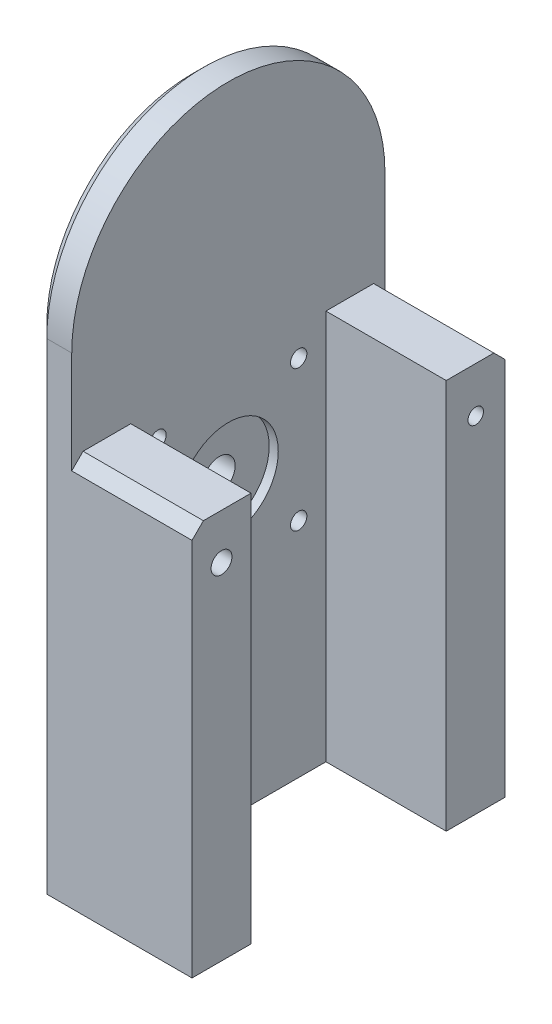
SolidWorks part; units mm, degrees
ref_plane "Ebene vorne" through (0, 0, 0) normal (0, 0, 1) x (1, 0, 0)
ref_plane "Ebene oben" through (0, 0, 0) normal (0, 1, 0) x (1, 0, 0)
ref_plane "Ebene rechts" through (0, 0, 0) normal (1, 0, 0) x (0, 0, -1)
sketch "Sketch2" plane through (0, 0, 0) normal (1, 0, 0) x (0, 0, -1)
  line L1 (0, 0) -> (69, 0)
  line L2 (0, 0) -> (0, 86)
  line L3 (0, 86) -> (69, 86)
  line L4 (69, 0) -> (69, 86)
  line L5 (0, 0) -> (69, 86) construction
  line L6 (0, 86) -> (69, 0) construction
  line L7 (0, 86) -> (69, 86)
  line L8 (0, 86) -> (0, 106)
  line L9 (0, 106) -> (69, 106)
  line L10 (69, 86) -> (69, 106)
  line L11 (0, 86) -> (69, 106) construction
  line L12 (0, 106) -> (69, 86) construction
  circle A0 centre (34.5, 106) radius 34.5
  point P4 (34.5, 43)
  point P9 (34.5, 96)
  dimension "D1" = 69
  dimension "D2" = 86
  dimension "D3" = 20
extrude "Boss-Extrude1" add sketch "Sketch2" along normal blind 34.5 contours A0 L3 L2 L1 L4 | L7 A0 region at (0, 39.049, -34.5) region at (0, 80.0809, -34.5)
sketch "Sketch9" plane through (34.5, 0, 0) normal (1, 0, 0) x (0, 0, -1)
  line L0 (13, 86) -> (13, 0)
  line L1 (0, 86) -> (69, 86) construction
  line L2 (0, 0) -> (69, 0) construction
  line L3 (13, 0) -> (56, 0)
  line L4 (56, 0) -> (56, 86)
  line L5 (56, 86) -> (13, 86)
  line L6 (0, 0) -> (0, 86) construction
  line L7 (69, 0) -> (69, 86) construction
  line L9 (13, 0) -> (56, 0)
  line L10 (13, 0) -> (13, 43)
  line L11 (13, 43) -> (56, 43)
  line L12 (56, 0) -> (56, 43)
  line L13 (13, 0) -> (56, 43) construction
  line L14 (13, 43) -> (56, 0) construction
  line L15 (56, 43) -> (13, 43)
  line L16 (56, 43) -> (56, 86)
  line L17 (56, 86) -> (13, 86)
  line L18 (13, 43) -> (13, 86)
  line L19 (56, 43) -> (13, 86) construction
  line L20 (56, 86) -> (13, 43) construction
  circle A0 centre (34.5, 64.5) radius 11
  circle A1 centre (34.5, 64.5) radius 3.5
  point P15 (34.5, 21.5)
  point P19 (34.5, 64.5)
  line M2 (69, 86) -> (0, 86)
  line M4 (0, 0) -> (69, 0)
  dimension "D3" = 22
  dimension "D4" = 7
  dimension "D1" = 13
  dimension "D2" = 13
extrude "Cut-Extrude1" cut sketch "Sketch9" against normal offset from surface (26.5 mm away) 8 contours L0 L11 L4 A0 M2 | A0 A1 | A1 | L11 L0 L4 M4 region at (34.5, 85.3919, -34.5) region at (34.5, 21.5, -34.5) region at (34.5, 64.5, -23.8111) region at (34.5, 64.5, -34.5) up to face at (0, 43, -34.5)
extrude "Boss-Extrude2" add sketch "Sketch2<5>" along normal blind 8 contours L9 A0 L7 | A0 L8 L3 | A0 L3 L10 | L9 A0 region at (0, 90.9027, -1.8818) region at (0, 90.9027, -67.1182) region at (0, 96.321, -34.5) region at (0, 120.6423, -34.5)
sketch "Sketch2<5>" plane through (0, 0, 0) normal (1, 0, 0) x (0, 0, -1) same geometry as "Sketch2"
extrude "Cut-Extrude2" cut sketch "Sketch9<3>" against normal offset from surface (28.5 mm away) 2 contours A0 A1 | A1 region at (34.5, 64.5, -23.8111) region at (34.5, 64.5, -34.5) up to face at (8, 73.8125, -34.5) offset beyond the face yes
sketch "Sketch9<3>" plane through (34.5, 0, 0) normal (1, 0, 0) x (0, 0, -1) same geometry as "Sketch9"
extrude "Cut-Extrude3" cut sketch "Sketch9<4>" against normal through all contours A1 region at (34.5, 64.5, -34.5)
sketch "Sketch9<4>" plane through (34.5, 0, 0) normal (1, 0, 0) x (0, 0, -1) same geometry as "Sketch9"
hole_wizard "CBORE for M3 Hex Socket Head Cap Screw1" positions "Sketch10" profile "Sketch11" counterbore size "M3" standard "DIN" end condition through all
sketch "Sketch10" plane through (0, 0, 0) normal (-1, 0, 0) x (0, 0, 1)
  line L1 (-50, 49) -> (-19, 49)
  line L2 (-50, 49) -> (-50, 80)
  line L3 (-50, 80) -> (-19, 80)
  line L4 (-19, 49) -> (-19, 80)
  line L5 (-50, 49) -> (-19, 80) construction
  line L6 (-50, 80) -> (-19, 49) construction
  point P1 (-34.5, 64.5)
  point P2 (-19, 80)
  point P5 (-50, 49)
  point P6 (-50, 80)
  point P7 (-19, 49)
  dimension "D1" = 31
sketch "Sketch11" plane through (0, 49, -19) normal (0, 1, 0) x (0, 0, 1)
  line L0 (0, 0) -> (0, 34.5)
  line L1 (0, 34.5) -> (1.8, 34.5)
  line L3 (1.8, 34.5) -> (1.8, 3.4)
  line L4 (1.8, 3.4) -> (3.25, 3.4)
  line L5 (3.25, 3.4) -> (3.25, 0)
  line L7 (3.25, 0) -> (0, 0)
  line L11 (0, -6.35) -> (0, 107.95) construction
  dimension "Thru Hole Dia." = 3.6
  dimension "Thru Hole Depth" = 34.5
  dimension "C'Bore Dia." = 6.5
  dimension "C'Bore Depth" = 3.4
hole_wizard "Ø4.6 (4.6) Diameter Hole1" positions "Sketch12" profile "Sketch13" hole size "Ø4.6" standard "DIN"
sketch "Sketch12" plane through (0, 0, 0) normal (0, -1, 0) x (-1, 0, 0)
  line L0 (-34.5, 69) -> (-34.5, 3.2341) construction
  line L1 (-34.5, 0) -> (-34.5, 13) construction
  line L4 (-65, 9.7341) -> (-4, 9.7341)
  line L5 (-65, 9.7341) -> (-65, 62.5)
  line L6 (-65, 62.5) -> (-4, 62.5)
  line L7 (-4, 9.7341) -> (-4, 62.5)
  line L8 (-65, 9.7341) -> (-4, 62.5) construction
  line L9 (-65, 62.5) -> (-4, 9.7341) construction
  line L10 (-34.5, 69) -> (0, 69) construction
  line L11 (0, 0) -> (0, 69) construction
  point P6 (-34.5, 36.117)
  point P7 (-4, 62.5)
  point P12 (-4, 9.7341)
  point P70 (-4, 36.117)
  dimension "D1" = 6.5
  dimension "D2" = 4
sketch "Sketch13" plane through (4, 0, -36.117) normal (1, 0, 0) x (0, 0, -1)
  line L0 (0, 0) -> (0, 7.382)
  line L1 (0, 7.382) -> (2.3, 6)
  line L2 (2.3, 6) -> (2.3, 0)
  line L5 (2.3, 0) -> (0, 0)
  line L10 (0, 7.382) -> (-2.3, 6) construction
  line L11 (0, -6.35) -> (0, 107.95) construction
  dimension "Hole Dia." = 4.6
  dimension "Hole Depth" = 6
  dimension "Drill Angle" = 118
hole_wizard "CBORE for M3 Hex Socket Head Cap Screw2" positions "Sketch16" profile "Sketch18" counterbore size "M3" standard "DIN" end condition through all
sketch "Sketch16" plane through (0, 0, 0) normal (-1, 0, 0) x (0, 0, 1)
  line L0 (-56, 86) -> (-69, 86) construction
  line L1 (-56, 86) -> (-69, 86)
  line L2 (-62.5, 86) -> (-62.5, 76) construction
  point P4 (-62.5, 76)
  dimension "D1" = 10
sketch "Sketch18" plane through (0, 76, -62.5) normal (0, 1, 0) x (0, 0, 1)
  line L0 (0, 0) -> (0, 34.5)
  line L1 (0, 34.5) -> (1.7, 34.5)
  line L3 (1.7, 34.5) -> (1.7, 3.4)
  line L4 (1.7, 3.4) -> (3.25, 3.4)
  line L5 (3.25, 3.4) -> (3.25, 0)
  line L7 (3.25, 0) -> (0, 0)
  line L11 (0, -6.35) -> (0, 107.95) construction
  dimension "Thru Hole Dia." = 3.4
  dimension "Thru Hole Depth" = 34.5
  dimension "C'Bore Dia." = 6.5
  dimension "C'Bore Depth" = 3.4
hole_wizard "Ø4.6 (4.6) Diameter Hole2" positions "Sketch14" profile "Sketch15" hole size "Ø4.6" standard "DIN"
sketch "Sketch14" plane through (34.5, 0, 0) normal (1, 0, 0) x (0, 0, -1)
  line L0 (6.5, 86) -> (6.5, 76) construction
  line L1 (0, 86) -> (13, 86) construction
  point P2 (6.5, 76)
  dimension "D1" = 10
sketch "Sketch15" plane through (34.5, 76, -6.5) normal (0, 1, 0) x (0, 0, -1)
  line L0 (0, 0) -> (0, 7.382)
  line L1 (0, 7.382) -> (2.3, 6)
  line L2 (2.3, 6) -> (2.3, 0)
  line L5 (2.3, 0) -> (0, 0)
  line L10 (0, 7.382) -> (-2.3, 6) construction
  line L11 (0, -6.35) -> (0, 107.95) construction
  dimension "Hole Dia." = 4.6
  dimension "Hole Depth" = 6
  dimension "Drill Angle" = 118
chamfer "2,5mm Chamfer1" distance 2.5 angle 45 5 edges at (21.25, 86, -69) (21.25, 86, 0) (0, 53, -69) (0, 140.5, -34.5) (0, 53, 0)
